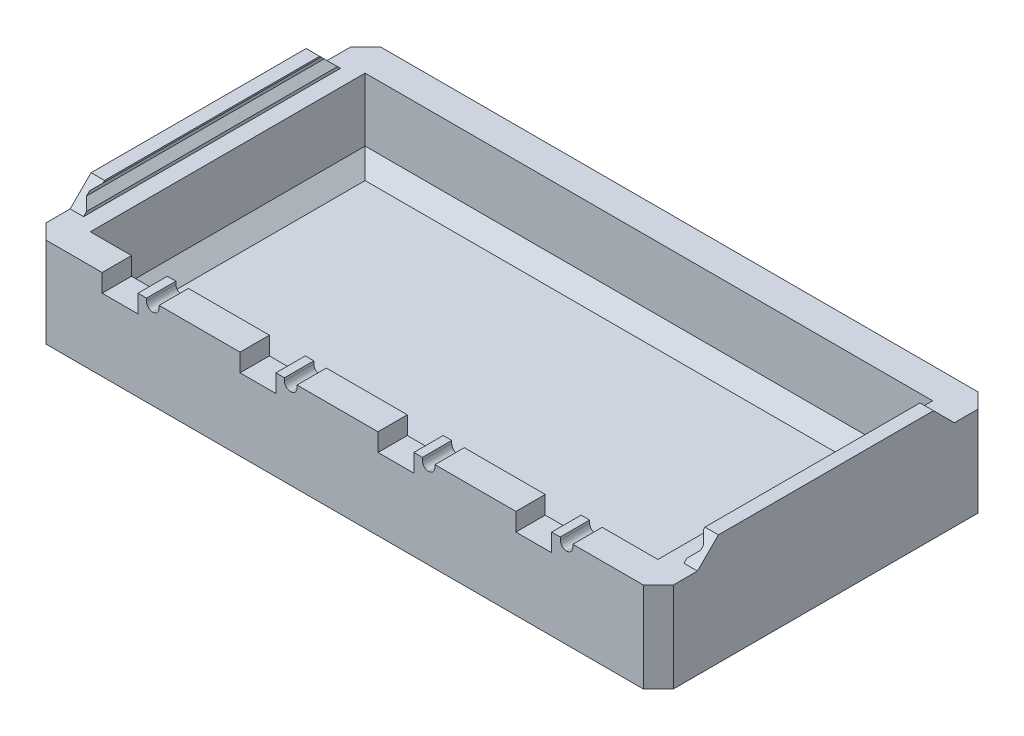
SolidWorks part; units mm, degrees
ref_plane "Front Plane" through (0, 0, 0) normal (0, 0, 1) x (1, 0, 0)
ref_plane "Top Plane" through (0, 0, 0) normal (0, 1, 0) x (1, 0, 0)
ref_plane "Right Plane" through (0, 0, 0) normal (1, 0, 0) x (0, 0, -1)
sketch "Sketch1" plane through (0, 0, 0) normal (0, 1, 0) x (1, 0, 0)
  line L0 (95, 46) -> (95, -46)
  line L1 (-95, 46) -> (95, 46)
  line L2 (-95, 46) -> (-95, -46)
  line L3 (-95, -46) -> (95, -46)
  line L4 (105, -55.8302) -> (-105, -55.8302)
  line L5 (-105, -55.8302) -> (-105, 56.1698)
  line L6 (-105, 56.1698) -> (105, 56.1698)
  line L7 (105, -55.8302) -> (105, 56.1698)
extrude "Boss-Extrude1" add sketch "Sketch1" along normal blind 30.16
sketch "Sketch2" plane through (0, 0, 0) normal (0, -1, 0) x (1, 0, 0)
  line L1 (-105, 55.8302) -> (105, 55.8302)
  line L2 (-105, 55.8302) -> (-105, -56.1698)
  line L3 (-105, -56.1698) -> (105, -56.1698)
  line L4 (105, 55.8302) -> (105, -56.1698)
extrude "Boss-Extrude2" add sketch "Sketch2" against normal blind 4
sketch "Sketch3" plane through (105, 0, 0) normal (1, 0, 0) x (0, 0, -1)
  line L1 (-55.8302, 30.16) -> (56.1698, 30.16) construction
  line L8 (-42.7385, 30.16) -> (43.2615, 30.16)
  line L10 (-35.7385, 37.16) -> (36.2615, 37.16)
  line L11 (-35.7385, 37.16) -> (-42.7385, 30.16)
  line L12 (36.2615, 37.16) -> (43.2615, 30.16)
  point P12 (0.1698, 30.16)
  point P13 (0.2615, 37.16)
extrude "Boss-Extrude3" add sketch "Sketch3" against normal blind 4.5
sketch "Sketch5" plane through (0, 0, 55.8302) normal (0, 0, 1) x (1, 0, 0)
  line L5 (69.3, 24.16) -> (69.3, 30.16)
  line L7 (57.3, 24.16) -> (69.3, 24.16)
  line L21 (57.3, 30.16) -> (57.3, 24.16)
  line L22 (23.13, 24.16) -> (23.13, 30.16)
  line L23 (11.13, 24.16) -> (23.13, 24.16)
  line L24 (11.13, 30.16) -> (11.13, 24.16)
  line L25 (-23.04, 24.16) -> (-23.04, 30.16)
  line L26 (-35.04, 24.16) -> (-23.04, 24.16)
  line L27 (-35.04, 30.16) -> (-35.04, 24.16)
  line L28 (-69.21, 24.16) -> (-69.21, 30.16)
  line L29 (-81.21, 24.16) -> (-69.21, 24.16)
  line L30 (-81.21, 30.16) -> (-81.21, 24.16)
  line L31 (-69.21, 30.16) -> (-81.21, 30.16)
  line L32 (-23.04, 30.16) -> (-35.04, 30.16)
  line L33 (23.13, 30.16) -> (11.13, 30.16)
  line L34 (69.3, 30.16) -> (57.3, 30.16)
extrude "Cut-Extrude2" cut sketch "Sketch5" against normal blind 14.5
sketch "Sketch6" plane through (0, 0, 55.8302) normal (0, 0, 1) x (1, 0, 0)
  line L6 (-62.15, 30.16) -> (-66.35, 30.16)
  line L7 (-62.15, 27.16) -> (-62.15, 30.16)
  line L8 (-66.35, 27.16) -> (-62.15, 27.16)
  line L9 (-66.35, 30.16) -> (-66.35, 27.16)
  line L10 (-15.98, 30.16) -> (-20.18, 30.16)
  line L11 (-15.98, 27.16) -> (-15.98, 30.16)
  line L24 (-20.18, 27.16) -> (-15.98, 27.16)
  line L25 (-20.18, 30.16) -> (-20.18, 27.16)
  line L26 (30.19, 30.16) -> (25.99, 30.16)
  line L27 (30.19, 27.16) -> (30.19, 30.16)
  line L28 (25.99, 27.16) -> (30.19, 27.16)
  line L29 (25.99, 30.16) -> (25.99, 27.16)
  line L30 (76.36, 30.16) -> (72.16, 30.16)
  line L31 (76.36, 27.16) -> (76.36, 30.16)
  line L32 (72.16, 27.16) -> (76.36, 27.16)
  line L33 (72.16, 30.16) -> (72.16, 27.16)
  dimension "D1" = 4.2
  dimension "D2" = 4.2
  dimension "D3" = 4.2
  dimension "D4" = 4.2
extrude "Cut-Extrude3" cut sketch "Sketch6" against normal blind 14.5
chamfer "Chamfer1" distance 5 angle 45 4 edges at (0, 4, 46) (95, 4, 0) (0, 4, -46) (-95, 4, 0)
chamfer "Chamfer2" distance 5 angle 45 4 edges at (-105, 15.08, -56.1698) (-105, 15.08, 55.8302) (105, 15.08, 55.8302) (105, 15.08, -56.1698)
sketch "Sketch7" plane through (0, 0, 55.8302) normal (0, 0, 1) x (1, 0, 0)
  line L0 (100.5, 36.66) -> (102.75, 34.41)
  line L1 (102.75, 33.41) -> (100.5, 31.16)
  line L2 (102.75, 34.41) -> (102.75, 33.41)
  line L3 (100.5, 36.66) -> (100.5, 31.16)
extrude "Cut-Extrude4" cut sketch "Sketch7" against normal blind 100
mirror "Mirror1" about plane through (0, 0, 0) normal (1, 0, 0) of "Boss-Extrude3", "Cut-Extrude4"
fillet "Fillet1" radius 2.1 8 edges at (76.36, 27.16, 50.9151) (30.19, 27.16, 50.9151) (-15.98, 27.16, 50.9151) (-62.15, 27.16, 50.9151) (72.16, 27.16, 50.9151) (25.99, 27.16, 50.9151) (-20.18, 27.16, 50.9151) (-66.35, 27.16, 50.9151)
